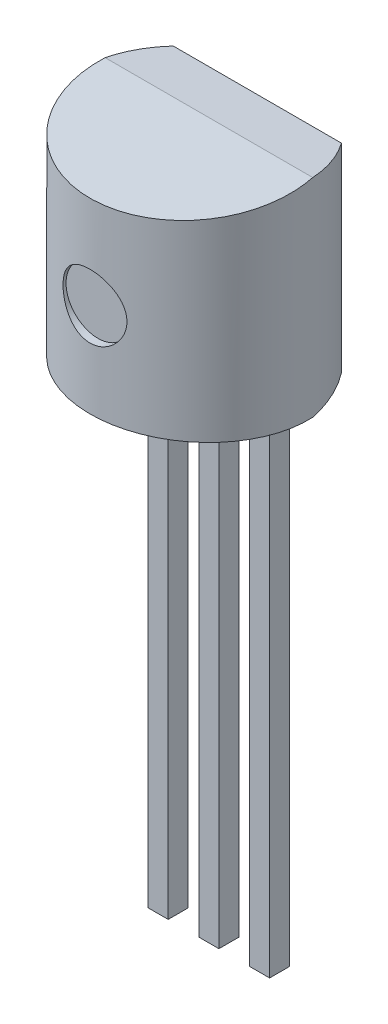
SolidWorks part; units mm, degrees
ref_plane "Front Plane" through (0, 0, 0) normal (0, 0, 1) x (1, 0, 0)
ref_plane "Top Plane" through (0, 0, 0) normal (0, 1, 0) x (1, 0, 0)
ref_plane "Right Plane" through (0, 0, 0) normal (1, 0, 0) x (0, 0, -1)
sketch "Sketch2" plane through (0, 0, 0) normal (0, 1, 0) x (1, 0, 0)
  line L0 (-2.6, 0) -> (2.6, 0) construction
  line L1 (-2.1054, 1.212) -> (2.1054, 1.212)
  line L2 (0, 0) -> (0, 1.212) construction
  arc A0 (-2.1054, 1.212) -> (2.1054, 1.212) centre (0, -0.354) ccw
  point P3 (0, 0)
  dimension "D1" = 4.19
  dimension "D2" = 5.2
  dimension "D3" = 2.27
extrude "Boss-Extrude1" add sketch "Sketch2" along normal mid plane 5.2
sketch "Sketch3" plane through (0, 2.6, 0) normal (0, 1, 0) x (1, 0, 0)
  line L0 (-2.6, 0) -> (2.6, 0) construction
  line L1 (-2.6, 0) -> (2.6, 0) construction
ref_plane "Plane1" through (0, 2.5803, -0.2257) normal (0, 0.9962, -0.0872) x (1, 0, 0)
ref_plane "Plane2" through (0, 2.5803, 0.2257) normal (0, 0.9962, 0.0872) x (1, 0, 0)
sketch "Sketch5" plane through (0, 2.5803, -0.2257) normal (0, 0.9962, -0.0872) x (1, 0, 0)
  line L1 (-4.9885, 2.0659) -> (6.8379, 2.0659)
  line L2 (-4.9885, 2.0659) -> (-4.9885, -3.5552)
  line L3 (-4.9885, -3.5552) -> (6.8379, -3.5552)
  line L4 (6.8379, 2.0659) -> (6.8379, -3.5552)
extrude "Cut-Extrude2" cut sketch "Sketch5" along normal through all
sketch "Sketch6" plane through (0, 2.5803, 0.2257) normal (0, 0.9962, 0.0872) x (1, 0, 0)
  line L1 (-5.588, 1.1618) -> (6.1027, 1.1618)
  line L2 (-5.588, 1.1618) -> (-5.588, -6.0928)
  line L3 (-5.588, -6.0928) -> (6.1027, -6.0928)
  line L4 (6.1027, 1.1618) -> (6.1027, -6.0928)
extrude "Cut-Extrude3" cut sketch "Sketch6" along normal blind 5.2
mirror "Mirror1" about plane through (0, 0, 0) normal (0, 1, 0) of "Cut-Extrude3", "Cut-Extrude2"
ref_plane "Plane3" through (0, -2.6, 0) normal (0, -1, 0) x (-1, 0, 0)
sketch "Sketch7" plane through (0, -2.6, 0) normal (0, -1, 0) x (-1, 0, 0)
  line L0 (-2.6, 0) -> (2.6, 0) construction
  line L1 (-1.52, 0) -> (-1.02, 0)
  line L2 (-1.52, 0) -> (-1.52, 0.5)
  line L3 (-1.52, 0.5) -> (-1.02, 0.5)
  line L4 (-1.02, 0) -> (-1.02, 0.5)
  line L5 (0, 0) -> (0, 0.5) construction
  line L6 (-0.25, 0) -> (0.25, 0)
  line L7 (-0.25, 0) -> (-0.25, 0.5)
  line L8 (-0.25, 0.5) -> (0.25, 0.5)
  line L9 (0.25, 0) -> (0.25, 0.5)
  line L10 (1.02, 0) -> (1.52, 0)
  line L11 (1.02, 0) -> (1.02, 0.5)
  line L12 (1.02, 0.5) -> (1.52, 0.5)
  line L13 (1.52, 0) -> (1.52, 0.5)
  line L14 (1.27, 0.5) -> (1.27, 0) construction
  line L15 (-1.27, 0.5) -> (-1.27, 0) construction
  dimension "D1" = 1.27
  dimension "D2" = 2.54
  dimension "D3" = 0.5
extrude "Boss-Extrude2" add sketch "Sketch7" along normal blind 12.7 and the other way up to body
ref_plane "Plane4" through (0, 0, 2.978) normal (0, 0, 1) x (1, 0, 0)
sketch "Sketch8" plane through (0, 0, 2.978) normal (0, 0, 1) x (1, 0, 0)
  circle A0 centre (0, 0) radius 0.8
  dimension "D1" = 1.6
extrude "Cut-Extrude4" cut sketch "Sketch8" against normal blind 0.2
sketch "Sketch9" plane through (0, 0, -1.212) normal (0, 0, -1) x (-1, 0, 0)
  line L0 (-1.3031, 0.1784) -> (1.2996, 0.1784) construction
  line L1 (-1.3031, -0.7444) -> (1.2996, -0.7444) construction
  text T0 "LM35" font "Arial" height in points 2
  text T1 "DZ" font "Arial" height in points 2
split line "Split Line1"
